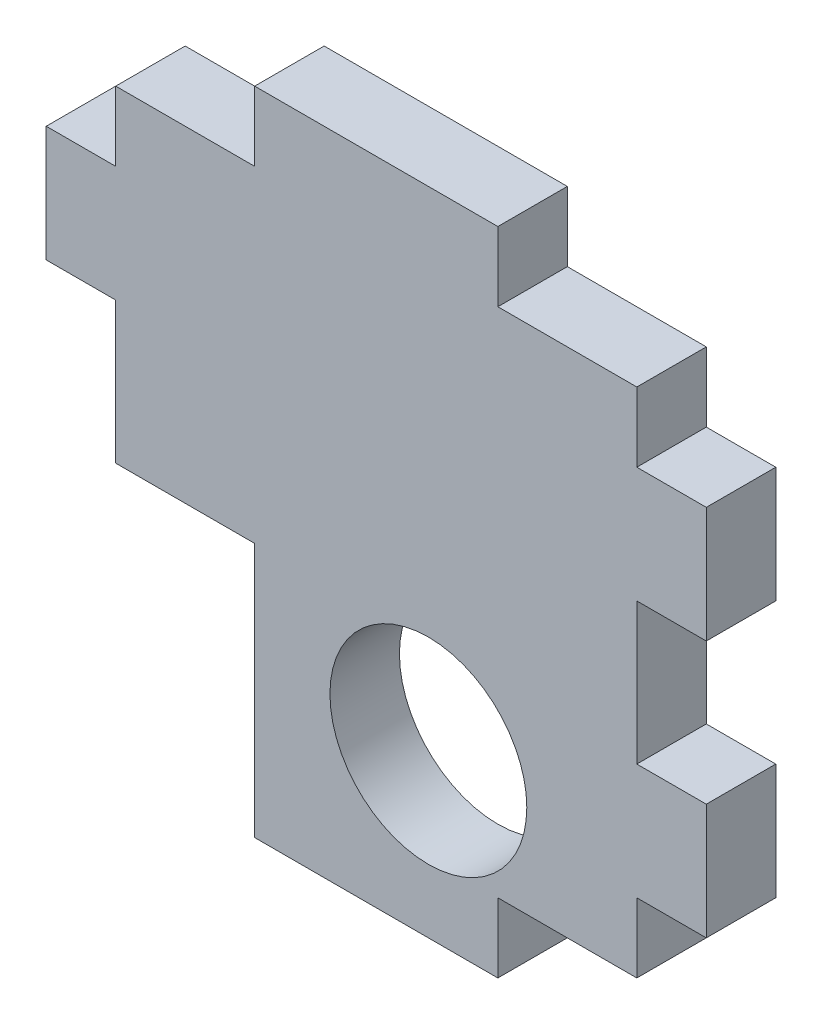
SolidWorks part; units mm, degrees
ref_plane "Plano frontal" through (0, 0, 0) normal (0, 0, 1) x (1, 0, 0)
ref_plane "Plano superior" through (0, 0, 0) normal (0, 1, 0) x (1, 0, 0)
ref_plane "Plano direito" through (0, 0, 0) normal (1, 0, 0) x (0, 0, -1)
sketch "BaseEsboco" plane through (0, 0, 0) normal (0, 0, 1) x (1, 0, 0)
  line L0 (0, 0) -> (6, 0)
  line L5 (6, 0) -> (6, -3)
  line L6 (6, -3) -> (16.5, -3)
  line L7 (16.5, -3) -> (16.5, 0)
  line L8 (16.5, 0) -> (22.5, 0)
  line L9 (22.5, 0) -> (22.5, 3)
  line L10 (22.5, 3) -> (25.5, 3)
  line L11 (25.5, 3) -> (25.5, 8)
  line L12 (25.5, 8) -> (22.5, 8)
  line L13 (22.5, 8) -> (22.5, 14.1)
  line L14 (22.5, 14.1) -> (25.5, 14.1)
  line L15 (25.5, 14.1) -> (25.5, 19.1)
  line L16 (25.5, 19.1) -> (22.5, 19.1)
  line L17 (22.5, 19.1) -> (22.5, 22.1)
  line L18 (22.5, 22.1) -> (16.5, 22.1)
  line L19 (16.5, 22.1) -> (16.5, 25.1)
  line L20 (16.5, 25.1) -> (6, 25.1)
  line L21 (6, 25.1) -> (6, 22.1)
  line L22 (6, 22.1) -> (0, 22.1)
  line L23 (0, 22.1) -> (0, 19.1)
  line L24 (0, 19.1) -> (-3, 19.1)
  line L25 (-3, 19.1) -> (-3, 14.1)
  line L26 (-3, 14.1) -> (0, 14.1)
  line L27 (0, 14.1) -> (0, 8)
  line L28 (0, 8) -> (-3, 8)
  line L29 (-3, 8) -> (-3, 3)
  line L30 (-3, 3) -> (0, 3)
  line L31 (0, 3) -> (0, 0)
  dimension "D1" = 28.1
  dimension "D2" = 28.5
  dimension "D3" = 9
  dimension "D4" = 9
  dimension "D5" = 6
  dimension "D6" = 5
  dimension "D7" = 6
  dimension "D8" = 5
  dimension "D9" = 3
  dimension "D10" = 3
  dimension "D11" = 3
  dimension "D12" = 3
extrude "Base" add sketch "BaseEsboco" along normal blind 3
sketch "Esboço1" plane through (0, 0, 3) normal (0, 0, 1) x (1, 0, 0)
  line L4 (0, 8) -> (6, 8)
  line L5 (6, 8) -> (6, 0)
  line L6 (6, 0) -> (0, 0)
  line L7 (0, 0) -> (0, 3)
  line L8 (0, 3) -> (-3, 3)
  line L9 (-3, 3) -> (-3, 8)
  line L10 (-3, 8) -> (0, 8)
  circle A0 centre (13.5, 4) radius 4.25
  dimension "D1" = 8.5
  dimension "D2" = 7
  dimension "D3" = 9
extrude "PassagemLEDeLDR" cut sketch "Esboço1" against normal blind 3
